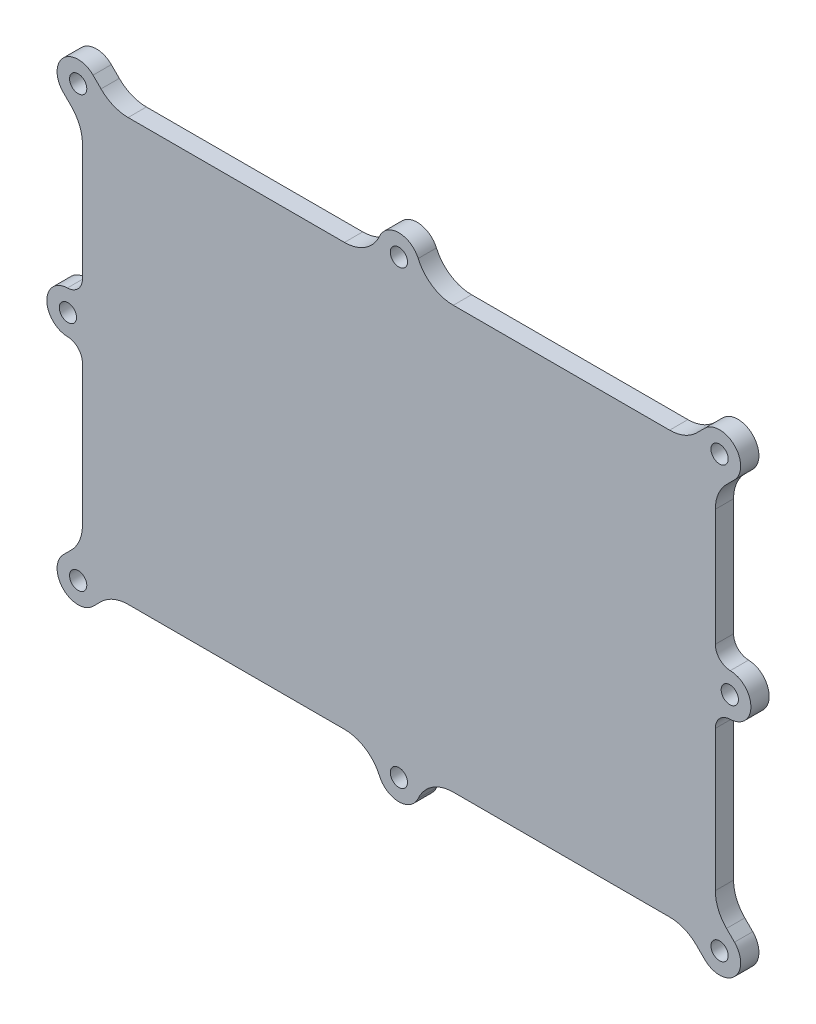
SolidWorks part; units mm, degrees
material "Custom Plastic"
ref_plane "X-Y Datum" through (0, 0, 0) normal (0, 0, 1) x (1, 0, 0)
ref_plane "X-Z Datum" through (0, 0, 0) normal (0, 1, 0) x (1, 0, 0)
ref_plane "Y-Z Datum" through (0, 0, 0) normal (1, 0, 0) x (0, 0, -1)
sketch "Sketch2" plane through (0, 0, 0) normal (0, 0, 1) x (1, 0, 0)
  line L16 (183.5533, 104.3328) -> (181.4806, 102.2601)
  line L17 (174.4096, 99.3312) -> (117.9783, 99.3312)
  line L18 (89.5814, 99.3312) -> (33.1502, 99.3312)
  line L19 (26.0791, 102.2601) -> (24.0065, 104.3328)
  line L20 (16.2283, 96.5546) -> (18.3009, 94.4819)
  line L21 (21.2299, 87.4109) -> (21.2299, 56.9084)
  line L22 (21.2299, 37.9134) -> (21.2299, 1.2515)
  line L23 (18.3009, -5.8196) -> (16.2283, -7.8922)
  line L24 (24.0065, -15.6704) -> (26.0791, -13.5977)
  line L25 (33.1502, -10.6688) -> (89.5814, -10.6688)
  line L26 (117.9783, -10.6688) -> (174.4096, -10.6688)
  line L27 (181.4806, -13.5977) -> (183.5533, -15.6704)
  line L28 (191.3314, -7.8922) -> (189.2588, -5.8196)
  line L29 (186.3299, 1.2515) -> (186.3299, 37.9134)
  line L30 (186.3299, 56.9084) -> (186.3299, 87.4109)
  line L31 (189.2588, 94.4819) -> (191.3314, 96.5546)
  line L32 (183.5533, 104.3328) -> (181.4806, 102.2601)
  line L33 (174.4096, 99.3312) -> (117.9783, 99.3312)
  line L34 (89.5814, 99.3312) -> (33.1502, 99.3312)
  line L35 (26.0791, 102.2601) -> (24.0065, 104.3328)
  line L36 (16.2283, 96.5546) -> (18.3009, 94.4819)
  line L37 (21.2299, 87.4109) -> (21.2299, 56.9084)
  line L38 (21.2299, 37.9134) -> (21.2299, 1.2515)
  line L39 (18.3009, -5.8196) -> (16.2283, -7.8922)
  line L40 (24.0065, -15.6704) -> (26.0791, -13.5977)
  line L41 (33.1502, -10.6688) -> (89.5814, -10.6688)
  line L42 (117.9783, -10.6688) -> (174.4096, -10.6688)
  line L43 (181.4806, -13.5977) -> (183.5533, -15.6704)
  line L44 (191.3314, -7.8922) -> (189.2588, -5.8196)
  line L45 (186.3299, 1.2515) -> (186.3299, 37.9134)
  line L46 (186.3299, 56.9084) -> (186.3299, 87.4109)
  line L47 (189.2588, 94.4819) -> (191.3314, 96.5546)
  arc A24 (174.4096, 99.3312) -> (181.4806, 102.2601) centre (174.4096, 109.3312) ccw
  arc A25 (108.818, 105.32) -> (117.9783, 99.3312) centre (117.9783, 109.3312) ccw
  arc A26 (108.818, 105.32) -> (98.7417, 105.32) centre (103.7799, 103.1139) ccw
  arc A27 (89.5814, 99.3312) -> (98.7417, 105.32) centre (89.5814, 109.3312) ccw
  arc A28 (26.0791, 102.2601) -> (33.1502, 99.3312) centre (33.1502, 109.3312) ccw
  arc A29 (24.0065, 104.3328) -> (16.2283, 96.5546) centre (20.1174, 100.4437) ccw
  arc A30 (21.2299, 87.4109) -> (18.3009, 94.4819) centre (11.2299, 87.4109) ccw
  arc A31 (17.3214, 52.9094) -> (21.2299, 56.9084) centre (17.2299, 56.9084) ccw
  arc A32 (17.3214, 52.9094) -> (17.3214, 41.9123) centre (17.4472, 47.4109) ccw
  arc A33 (21.2299, 37.9134) -> (17.3214, 41.9123) centre (17.2299, 37.9134) ccw
  arc A34 (18.3009, -5.8196) -> (21.2299, 1.2515) centre (11.2299, 1.2515) ccw
  arc A35 (16.2283, -7.8922) -> (24.0065, -15.6704) centre (20.1174, -11.7813) ccw
  arc A36 (33.1502, -10.6688) -> (26.0791, -13.5977) centre (33.1502, -20.6688) ccw
  arc A37 (98.7417, -16.6577) -> (89.5814, -10.6688) centre (89.5814, -20.6688) ccw
  arc A38 (98.7417, -16.6577) -> (108.818, -16.6577) centre (103.7799, -14.4515) ccw
  arc A39 (117.9783, -10.6688) -> (108.818, -16.6577) centre (117.9783, -20.6688) ccw
  arc A40 (181.4806, -13.5977) -> (174.4096, -10.6688) centre (174.4096, -20.6688) ccw
  arc A41 (183.5533, -15.6704) -> (191.3314, -7.8922) centre (187.4423, -11.7813) ccw
  arc A42 (186.3299, 1.2515) -> (189.2588, -5.8196) centre (196.3299, 1.2515) ccw
  arc A43 (190.2384, 41.9123) -> (186.3299, 37.9134) centre (190.3299, 37.9134) ccw
  arc A44 (190.2384, 41.9123) -> (190.2384, 52.9094) centre (190.1126, 47.4109) ccw
  arc A45 (186.3299, 56.9084) -> (190.2384, 52.9094) centre (190.3299, 56.9084) ccw
  arc A46 (189.2588, 94.4819) -> (186.3299, 87.4109) centre (196.3299, 87.4109) ccw
  arc A47 (191.3314, 96.5546) -> (183.5533, 104.3328) centre (187.4423, 100.4437) ccw
  arc A48 (174.4096, 99.3312) -> (181.4806, 102.2601) centre (174.4096, 109.3312) ccw
  arc A49 (108.818, 105.32) -> (117.9783, 99.3312) centre (117.9783, 109.3312) ccw
  arc A50 (108.818, 105.32) -> (98.7417, 105.32) centre (103.7799, 103.1139) ccw
  arc A51 (89.5814, 99.3312) -> (98.7417, 105.32) centre (89.5814, 109.3312) ccw
  arc A52 (26.0791, 102.2601) -> (33.1502, 99.3312) centre (33.1502, 109.3312) ccw
  arc A53 (24.0065, 104.3328) -> (16.2283, 96.5546) centre (20.1174, 100.4437) ccw
  arc A54 (21.2299, 87.4109) -> (18.3009, 94.4819) centre (11.2299, 87.4109) ccw
  arc A55 (17.3214, 52.9094) -> (21.2299, 56.9084) centre (17.2299, 56.9084) ccw
  arc A56 (17.3214, 52.9094) -> (17.3214, 41.9123) centre (17.4472, 47.4109) ccw
  arc A57 (21.2299, 37.9134) -> (17.3214, 41.9123) centre (17.2299, 37.9134) ccw
  arc A58 (18.3009, -5.8196) -> (21.2299, 1.2515) centre (11.2299, 1.2515) ccw
  arc A59 (16.2283, -7.8922) -> (24.0065, -15.6704) centre (20.1174, -11.7813) ccw
  arc A60 (33.1502, -10.6688) -> (26.0791, -13.5977) centre (33.1502, -20.6688) ccw
  arc A61 (98.7417, -16.6577) -> (89.5814, -10.6688) centre (89.5814, -20.6688) ccw
  arc A62 (98.7417, -16.6577) -> (108.818, -16.6577) centre (103.7799, -14.4515) ccw
  arc A63 (117.9783, -10.6688) -> (108.818, -16.6577) centre (117.9783, -20.6688) ccw
  arc A64 (181.4806, -13.5977) -> (174.4096, -10.6688) centre (174.4096, -20.6688) ccw
  arc A65 (183.5533, -15.6704) -> (191.3314, -7.8922) centre (187.4423, -11.7813) ccw
  arc A66 (186.3299, 1.2515) -> (189.2588, -5.8196) centre (196.3299, 1.2515) ccw
  arc A67 (190.2384, 41.9123) -> (186.3299, 37.9134) centre (190.3299, 37.9134) ccw
  arc A68 (190.2384, 41.9123) -> (190.2384, 52.9094) centre (190.1126, 47.4109) ccw
  arc A69 (186.3299, 56.9084) -> (190.2384, 52.9094) centre (190.3299, 56.9084) ccw
  arc A70 (189.2588, 94.4819) -> (186.3299, 87.4109) centre (196.3299, 87.4109) ccw
  arc A71 (191.3314, 96.5546) -> (183.5533, 104.3328) centre (187.4423, 100.4437) ccw
  dimension "D1" = 0
extrude "Boss-Extrude1" add sketch "Sketch2" along normal blind 4.7625
sketch "Sketch5" plane through (0, 0, 4.7625) normal (0, 0, 1) x (1, 0, 0)
  point P0 (17.4472, 47.4109)
  point P1 (20.1174, 100.4437)
  point P3 (103.7799, 103.1139)
  point P5 (187.4423, 100.4437)
  point P7 (190.1126, 47.4109)
  point P9 (187.4423, -11.7813)
  point P11 (103.7799, -14.4515)
  point P13 (20.1174, -11.7813)
hole_wizard "M4 Clearance Hole1" positions "Sketch5" profile "Sketch6" hole size "M4" standard "ANSI Metric" end condition through all
sketch "Sketch6" plane through (17.4472, 47.4109, 4.7625) normal (1, 0, 0) x (0, -1, 0)
  line L0 (0, 0) -> (0, 4.7625)
  line L1 (0, 4.7625) -> (2.25, 4.7625)
  line L2 (2.25, 4.7625) -> (2.25, 0)
  line L5 (2.25, 0) -> (0, 0)
  line L11 (0, -6.35) -> (0, 107.95) construction
  dimension "Thru Hole Dia." = 4.5
  dimension "Thru Hole Depth" = 4.7625
